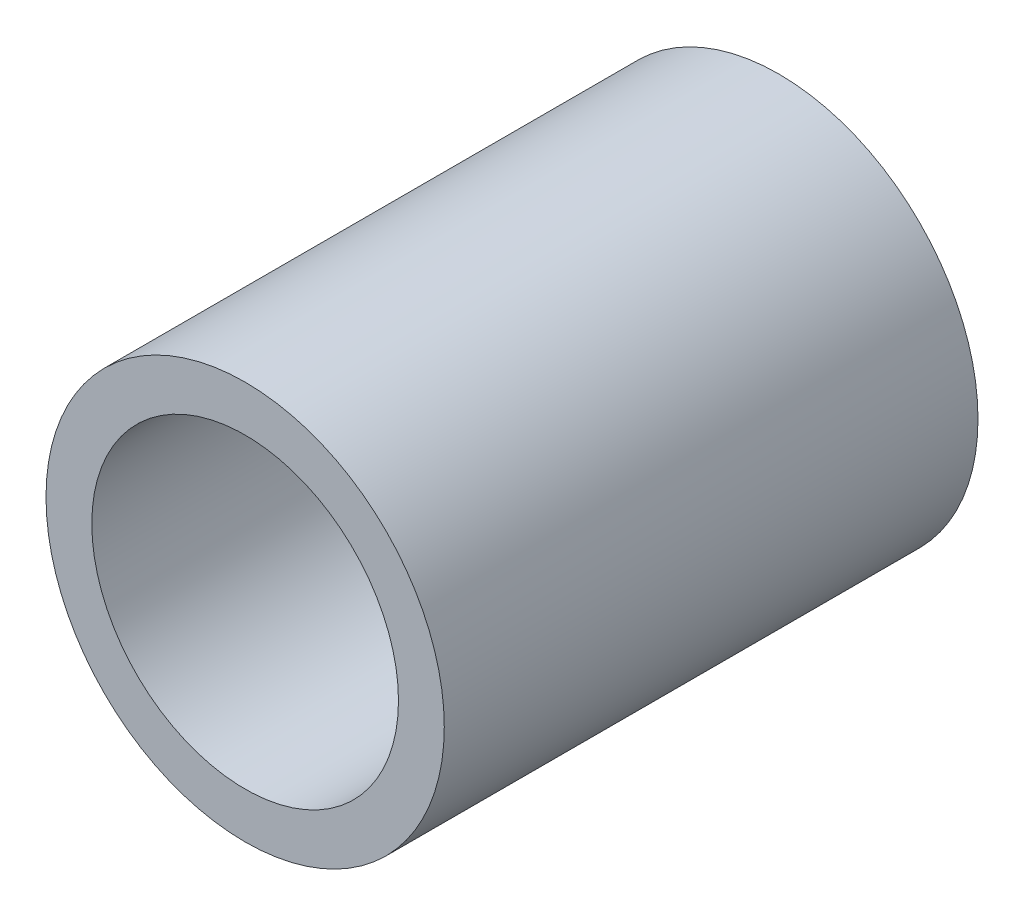
SolidWorks part; units mm, degrees
material "Delrin 2700 NC010, Low Viscosity Acetal Copolymer (SS)"
ref_plane "Front" through (0, 0, 0) normal (0, 0, 1) x (1, 0, 0)
ref_plane "Top" through (0, 0, 0) normal (0, 1, 0) x (1, 0, 0)
ref_plane "Right" through (0, 0, 0) normal (1, 0, 0) x (0, 0, -1)
sketch "Sketch1" plane through (0, 0, 0) normal (0, 0, 1) x (1, 0, 0)
  circle A0 centre (0, 0) radius 4.8895
  circle A1 centre (0, 0) radius 6.35
  dimension "D1" = 9.779
  dimension "D2" = 12.7
extrude "Boss-Extrude1" add sketch "Sketch1" along normal blind 17.018
